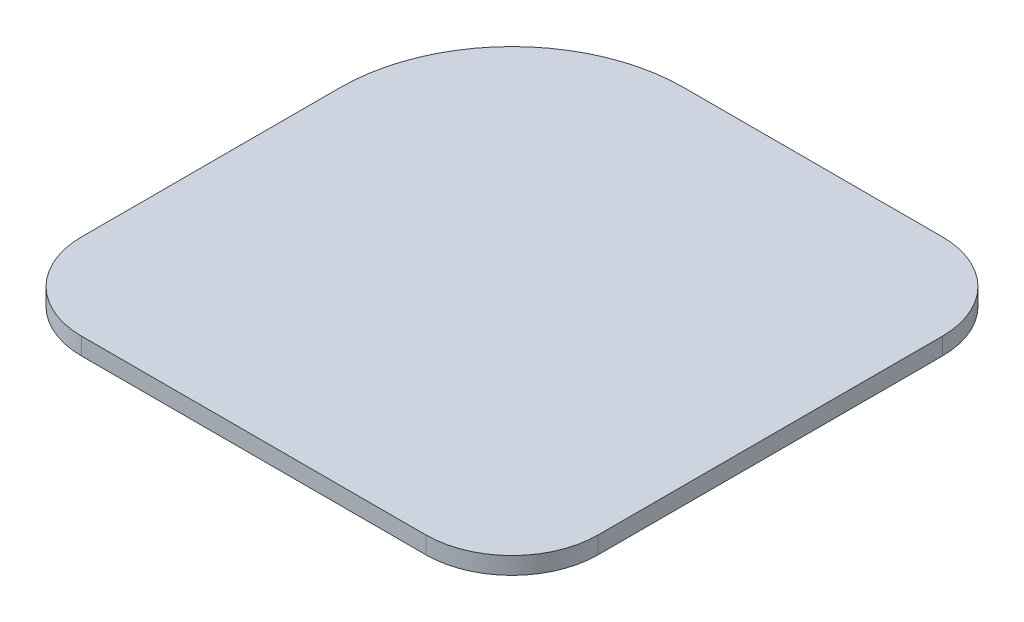
SolidWorks part; units mm, degrees
ref_plane "Front Plane" through (0, 0, 0) normal (0, 0, 1) x (1, 0, 0)
ref_plane "Top Plane" through (0, 0, 0) normal (0, 1, 0) x (1, 0, 0)
ref_plane "Right Plane" through (0, 0, 0) normal (1, 0, 0) x (0, 0, -1)
sketch "Sketch2" plane through (0, 0, 0) normal (0, 1, 0) x (1, 0, 0)
  line L1 (-10, 30) -> (20, 30)
  line L2 (-30, 10) -> (-30, -20)
  line L3 (-20, -30) -> (20, -30)
  line L4 (30, 20) -> (30, -20)
  line L5 (-30, 30) -> (30, -30) construction
  line L6 (-30, -30) -> (30, 30) construction
  arc A0 (-10, 30) -> (-30, 10) centre (-10, 10) ccw
  arc A1 (-30, -20) -> (-20, -30) centre (-20, -20) ccw
  arc A2 (20, -30) -> (30, -20) centre (20, -20) ccw
  arc A3 (20, 30) -> (30, 20) centre (20, 20) cw
  point P0 (0, 0)
  dimension "D3" = 20
  dimension "D4" = 10
  dimension "D1" = 60
  dimension "D2" = 60
extrude "Boss-Extrude1" add sketch "Sketch2" along normal blind 2
scale "Scale1" scale about centroid uniform scaling yes scale factor 0.9
